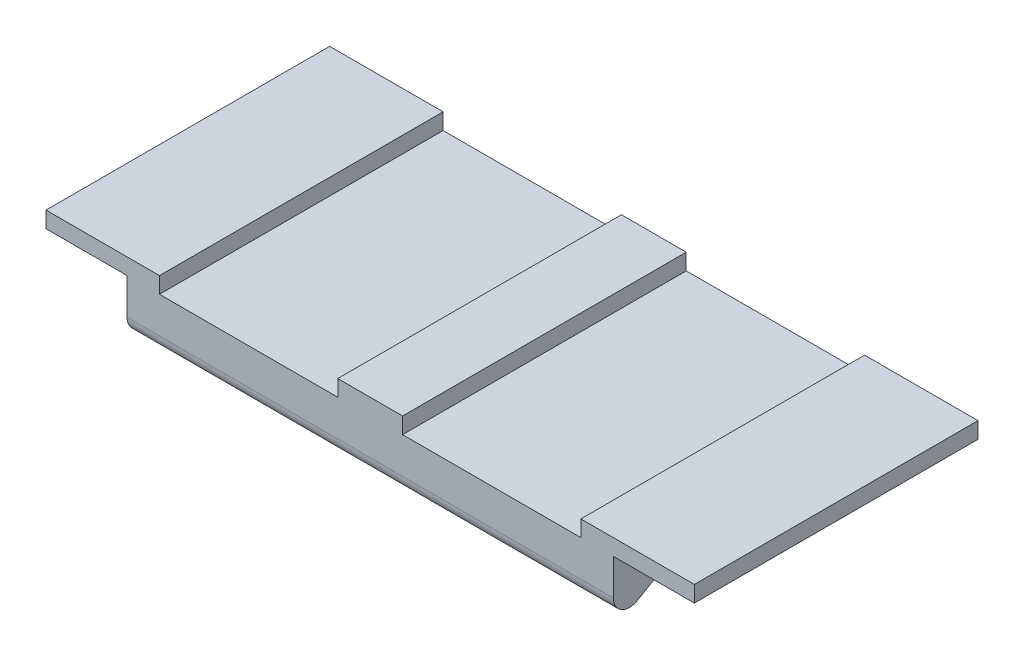
SolidWorks part; units mm, degrees
material "PEI"
ref_plane "Front Plane" through (0, 0, 0) normal (0, 0, 1) x (1, 0, 0)
ref_plane "Top Plane" through (0, 0, 0) normal (0, 1, 0) x (1, 0, 0)
ref_plane "Right Plane" through (0, 0, 0) normal (1, 0, 0) x (0, 0, -1)
sketch "Sketch1" plane through (0, 0, 0) normal (0, 1, 0) x (1, 0, 0)
  line L1 (30, -17.5) -> (-30, -17.5)
  line L2 (30, -17.5) -> (30, 17.5)
  line L3 (30, 17.5) -> (-30, 17.5)
  line L4 (-30, -17.5) -> (-30, 17.5)
  line L5 (30, -17.5) -> (-30, 17.5) construction
  line L6 (30, 17.5) -> (-30, -17.5) construction
  point P0 (0, 0)
  dimension "D1" = 35
  dimension "D2" = 60
extrude "Boss-Extrude1" add sketch "Sketch1" against normal blind 10
sketch "Sketch2" plane through (30, 0, 0) normal (1, 0, 0) x (0, 0, -1)
  line L0 (-17.5, -10) -> (-12.5, -7)
  line L1 (-12.5, -7) -> (12.5, -7)
  line L2 (0, -7) -> (0, -10)
  line L3 (17.5, -10) -> (12.5, -7)
  line L4 (17.5, 0) -> (-17.5, 0)
  line L5 (-17.5, 0) -> (-17.5, -10)
  line L6 (-17.5, -10) -> (17.5, -10)
  line L7 (17.5, -10) -> (17.5, 0)
  line L8 (17.5, 0) -> (-17.5, 0)
  line L9 (-17.5, 0) -> (-17.5, -10)
  line L10 (-17.5, -10) -> (17.5, -10)
  line L11 (17.5, -10) -> (17.5, 0)
  line M7 (-17.5, -10) -> (17.5, -10)
  dimension "D2" = 5
  dimension "D3" = 3
  dimension "D1" = 0
extrude "Cut-Extrude1" cut sketch "Sketch2" against normal through all and the other way through all contours L2 L1 L0 M7 | L3 L1 L2 M7 region at (30, -8.5833, 7.5694) region at (30, -8.5833, -7.5694)
fillet "Fillet1" radius 2 4 edges at (0, -7, 12.5) (0, -7, -12.5) (0, -10, -17.5) (0, -10, 17.5)
sketch "Sketch3" plane through (0, 0, 17.5) normal (0, 0, 1) x (1, 0, 0)
  line L0 (-30, 0) -> (30, 0) construction
  line L1 (-26, 2) -> (-4, 2)
  line L2 (-26, 2) -> (-26, -2)
  line L3 (-26, -2) -> (-4, -2)
  line L4 (-30, 0) -> (-30, -6.4676)
  line L5 (-30, -6.4676) -> (30, -6.4676)
  line L6 (30, -6.4676) -> (30, 0)
  line L7 (30, 0) -> (-30, 0)
  line L8 (-30, 0) -> (-30, -6.4676)
  line L9 (-30, -6.4676) -> (30, -6.4676)
  line L10 (30, -6.4676) -> (30, 0)
  line L11 (30, 0) -> (-30, 0)
  line L12 (-4, 2) -> (-4, -2)
  line L13 (-26, 2) -> (-4, -2) construction
  line L14 (-26, -2) -> (-4, 2) construction
  line L15 (0, 0) -> (0, -6.4676)
  line L16 (26, -2) -> (4, 2) construction
  line L17 (26, 2) -> (4, -2) construction
  line L18 (4, 2) -> (4, -2)
  line L19 (26, -2) -> (4, -2)
  line L20 (26, 2) -> (26, -2)
  line L21 (26, 2) -> (4, 2)
  point P2 (-15, 0)
  point P13 (0, 0)
  point P18 (15, 0)
  dimension "D2" = 22
  dimension "D3" = 4
  dimension "D4" = 15
  dimension "D1" = 0
extrude "Cut-Extrude2" cut sketch "Sketch3" against normal through all contours L12 L11 L2 L3 | L20 L11 L18 L19 region at (-15, -1, 17.5) region at (15, -1, 17.5)
sketch "Sketch5" plane through (-30, 0, 0) normal (-1, 0, 0) x (0, 0, 1)
  line L1 (-17.5, 0) -> (17.5, 0)
  line L2 (-17.5, 0) -> (-17.5, -2)
  line L3 (-17.5, -2) -> (17.5, -2)
  line L4 (17.5, 0) -> (17.5, -2)
  line L6 (-17.5, 0) -> (-17.5, -6.4676)
  line L7 (-14.471, -8.1826) -> (-12.975, -7.285)
  line L8 (-11.946, -7) -> (11.946, -7)
  line L9 (12.975, -7.285) -> (14.471, -8.1826)
  line L10 (17.5, -6.4676) -> (17.5, 0)
  line L11 (17.5, 0) -> (-17.5, 0)
  line L12 (-17.5, 0) -> (-17.5, -6.4676)
  line L13 (-14.471, -8.1826) -> (-12.975, -7.285)
  line L14 (-11.946, -7) -> (11.946, -7)
  line L15 (12.975, -7.285) -> (14.471, -8.1826)
  line L16 (17.5, -6.4676) -> (17.5, 0)
  line L17 (17.5, 0) -> (-17.5, 0)
  arc A4 (-17.5, -6.4676) -> (-14.471, -8.1826) centre (-15.5, -6.4676) ccw
  arc A5 (-11.946, -7) -> (-12.975, -7.285) centre (-11.946, -9) ccw
  arc A6 (12.975, -7.285) -> (11.946, -7) centre (11.946, -9) ccw
  arc A7 (14.471, -8.1826) -> (17.5, -6.4676) centre (15.5, -6.4676) ccw
  arc A8 (-17.5, -6.4676) -> (-14.471, -8.1826) centre (-15.5, -6.4676) ccw
  arc A9 (-11.946, -7) -> (-12.975, -7.285) centre (-11.946, -9) ccw
  arc A10 (12.975, -7.285) -> (11.946, -7) centre (11.946, -9) ccw
  arc A11 (14.471, -8.1826) -> (17.5, -6.4676) centre (15.5, -6.4676) ccw
  line M13 (-17.5, 0) -> (-17.5, -6.4676)
  line M21 (17.5, -6.4676) -> (17.5, 0)
  line M22 (17.5, 0) -> (-17.5, 0)
  dimension "D2" = 2
  dimension "D1" = 0
extrude "Boss-Extrude2" add sketch "Sketch5" along normal blind 10 contours L3 M13 M21 M22 region at (-30, -1, 0)
mirror "Mirror1" about plane through (0, 0, 0) normal (1, 0, 0) of "Boss-Extrude2"
